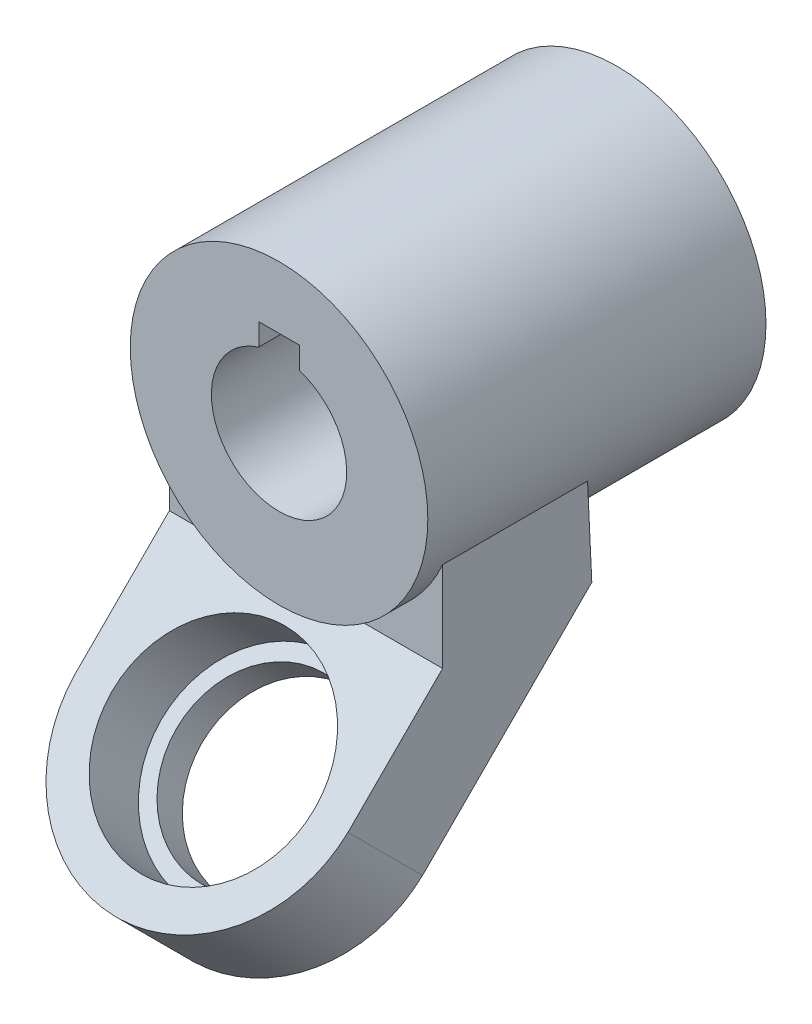
SolidWorks part; units mm, degrees
ref_plane "Plan de face" through (0, 0, 0) normal (0, 0, 1) x (1, 0, 0)
ref_plane "Plan de dessus" through (0, 0, 0) normal (0, 1, 0) x (1, 0, 0)
ref_plane "Plan de droite" through (0, 0, 0) normal (1, 0, 0) x (0, 0, -1)
sketch "Esquisse1" plane through (0, 0, 0) normal (0, 0, 1) x (1, 0, 0)
  line L0 (-3, 12.8) -> (3, 12.8)
  line L1 (3, 12.8) -> (3, 9.5394)
  line L2 (-3, 12.8) -> (-3, 9.5394)
  line L3 (0, 0) -> (0, 43.3103) construction
  circle A0 centre (0, 0) radius 22
  circle A1 centre (0, 0) radius 10
  point P6 (0, 12.8)
  dimension "D1" = 44
  dimension "D2" = 20
  dimension "D3" = 6
  dimension "D4" = 12.8
extrude "Boss.-Extru.1" add sketch "Esquisse1" along normal blind 25 and the other way blind 25 contours A1 L2 L0 A0 L1 region at (-21.3777, 0, 0)
sketch "Esquisse2" plane through (0, 0, 25) normal (0, 0, 1) x (1, 0, 0)
  line L0 (-22, 0) -> (-21.6763, -22) construction
  line L1 (-21.6763, -22) -> (0, -22) construction
  circle A0 centre (0, 0) radius 22 construction
sketch "Esquisse4" plane through (0, 0, 0) normal (1, 0, 0) x (0, 0, -1)
  line L0 (-71, 0) -> (25, 0) construction
  line L1 (-71, 0) -> (-35.0083, -35.9917) construction
  line L2 (1.0452, -22) -> (-37.9691, -61.0143)
  line L3 (-37.9691, -61.0143) -> (-49, -49.9835)
  line L4 (-49, -49.9835) -> (-21.0165, -22)
  line L5 (-21.0165, -22) -> (-21.0165, 0)
  line L6 (-21.0165, 0) -> (0, 0)
  line L7 (0, 0) -> (1.0452, -22)
  line L8 (-36.456, 0) -> (-36.456, -22) construction
  line L9 (-36.456, -22) -> (29.1192, -22) construction
  dimension "D1" = 96
  dimension "D2" = 15.6
  dimension "D3" = 50.9
  dimension "D4" = 45
  dimension "D5" = 22
extrude "Boss.-Extru.2" add sketch "Esquisse4" along normal blind 20.2 and the other way blind 20.2
sketch "Esquisse5" plane through (0, -0.4917, -0.4917) normal (0, 0.7071, 0.7071) x (1, 0, 0)
  line L0 (-20.2, -69.9919) -> (20.2, -69.9919) construction
  line L1 (0, 0) -> (0, -49.7919) construction
  circle A0 centre (0, -49.7919) radius 15
  dimension "D1" = 30
  dimension "D2" = 20.2
extrude "Enlèv. mat.-Extru.1" cut sketch "Esquisse5" against normal blind 10.3
sketch "Esquisse7" plane through (0, -0.4917, -0.4917) normal (0, 0.7071, 0.7071) x (1, 0, 0)
  line L0 (0, 0) -> (0, -49.7919) construction
  line L1 (-20.2, -69.9919) -> (20.2, -69.9919) construction
  circle A0 centre (0, -49.7919) radius 12.75
  dimension "D2" = 25.5
  dimension "D1" = 20.2
extrude "Enlèv. mat.-Extru.3" cut sketch "Esquisse7" against normal through all
sketch "Esquisse8" plane through (0, 0, 25) normal (0, 0, 1) x (1, 0, 0)
  circle A0 centre (0, 0) radius 10
  dimension "D1" = 20
extrude "Enlèv. mat.-Extru.4" cut sketch "Esquisse8" against normal through all
sketch "Esquisse9" plane through (0, 0, -25) normal (0, 0, -1) x (-1, 0, 0)
  circle A0 centre (0, 0) radius 18
  dimension "D1" = 36
extrude "Enlèv. mat.-Extru.5" cut sketch "Esquisse9" against normal blind 2
sketch "Esquisse10" plane through (0, -0.4917, -0.4917) normal (0, 0.7071, 0.7071) x (1, 0, 0)
  line L0 (20.2, -30.4173) -> (20.2, -69.9919) construction
  line L1 (-20.2, -30.4173) -> (-20.2, -69.9919) construction
  circle A0 centre (0, -49.7919) radius 12.75 construction
  circle A1 centre (0, -49.7919) radius 12.75
  arc A2 (20.2, -50.2046) -> (-20.2, -49.3792) centre (0, -49.7919) cw
sketch "Esquisse11" plane through (0, -0.4917, -0.4917) normal (0, 0.7071, 0.7071) x (1, 0, 0)
  line L0 (-20.2, -49.3792) -> (-20.2, -69.9919)
  line L1 (-20.2, -69.9919) -> (20.2, -69.9919)
  line L2 (20.2, -69.9919) -> (20.2, -50.2046)
  arc A0 (20.2, -50.2046) -> (-20.2, -50.2046) centre (0, -49.7919) cw
  line M2 (-20.2, -69.9919) -> (20.2, -69.9919)
  line M3 (20.2, -69.9919) -> (20.2, -30.4173)
extrude "Enlèv. mat.-Extru.6" cut sketch "Esquisse11" against normal through all contours A0 M3 M2 | A0 L0 M2 region at (-15.6921, -46.7959, 45.8125) region at (15.6921, -46.7959, 45.8125)
